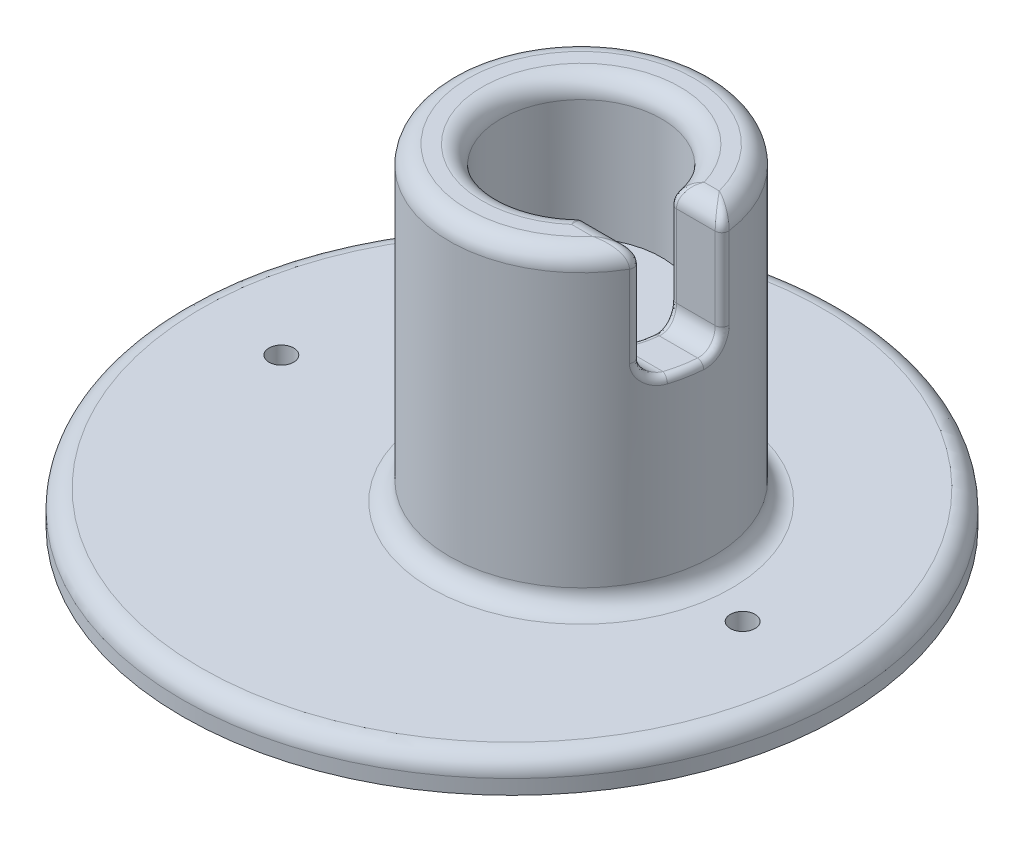
SolidWorks part; units mm, degrees
material "ABS"
ref_plane "Front Plane" through (0, 0, 0) normal (0, 0, 1) x (1, 0, 0)
ref_plane "Top Plane" through (0, 0, 0) normal (0, 1, 0) x (1, 0, 0)
ref_plane "Right Plane" through (0, 0, 0) normal (1, 0, 0) x (0, 0, -1)
sketch "Sketch1" plane through (0, 0, 0) normal (0, 1, 0) x (1, 0, 0)
  circle A0 centre (0, 0) radius 7.62
  circle A1 centre (0, 0) radius 63.5
  dimension "D1" = 127
  dimension "D2" = 15.24
extrude "Boss-Extrude1" add sketch "Sketch1" along normal blind 6.35
sketch "Sketch2" plane through (0, 6.35, 0) normal (0, 1, 0) x (1, 0, 0)
  line L0 (9, 11.3527) -> (9, -3.5148) construction
  line L1 (8.89, 4.445) -> (9, 4.445) construction
  circle A0 centre (8.89, 4.445) radius 25.4
  circle A3 centre (8.89, 4.445) radius 15.494
  dimension "D1" = 50.8
  dimension "D2" = 4.445
  dimension "D3" = 30.988
  dimension "D4" = 9
extrude "Boss-Extrude2" add sketch "Sketch2" along normal blind 59.69
sketch "Sketch3" plane through (0, 66.04, 0) normal (0, 1, 0) x (1, 0, 0)
  line L8 (43.18, 6.35) -> (43.18, -6.35)
  line L9 (-1.27, 6.35) -> (43.18, 6.35)
  line L13 (-1.27, 6.35) -> (-1.27, -6.35)
  line L14 (-1.27, -6.35) -> (43.18, -6.35)
  circle A0 centre (0, 0) radius 7.62 construction
  dimension "D5" = 6.35
  dimension "D1" = 1.27
  dimension "D2" = 12.7
  dimension "D3" = 44.45
extrude "Cut-Extrude1" cut sketch "Sketch3" against normal blind 22.86
sketch "Sketch4" plane through (0, 6.35, 0) normal (0, 1, 0) x (1, 0, 0)
  circle A0 centre (44.45, 0) radius 2.3812
  circle A1 centre (-44.45, 0) radius 2.3812
  dimension "D1" = 4.7625
  dimension "D2" = 4.7625
  dimension "D3" = 44.45
  dimension "D4" = 44.45
extrude "Cut-Extrude2" cut sketch "Sketch4" against normal through all
fillet "Fillet1" radius 3.556 8 edges at (-16.0907, 66.04, -9.041) (29.2425, 66.04, -6.35) (-5.7989, 66.04, -9.3744) (25.9432, 66.04, 6.35) (25.9432, 43.18, 6.35) (29.2425, 43.18, -6.35) (8.89, 6.35, 20.955) (0, 6.35, 63.5)
fillet "Fillet2" radius 1.27 1 edges at (22.7483, 6.35, -11.3741)
fillet "Fillet3" radius 1.27 14 edges at (20.4615, 44.9324, 5.8587) (20.2892, 64.5782, 7.032) (30.8341, 64.5341, 7.0004) (24.7056, 64.309, -6.8541) (24.3749, 43.9279, -4.9757) (33.7516, 64.1773, -6.779) (20.0045, 54.61, 6.35) (31.8819, 54.61, 6.35) (24.2664, 54.61, -6.35) (34.2185, 54.61, -6.35) (23.7082, 43.18, 0.0812) (32.4276, 44.0307, 5.1019) (33.893, 43.18, 0.028) (34.2649, 44.5173, -5.573)
sketch "Sketch5" plane through (0, 6.35, 0) normal (0, 1, 0) x (1, 0, 0)
  circle A0 centre (8.89, 4.445) radius 15.494
extrude "Boss-Extrude3" add sketch "Sketch5" along normal blind 33.02
sketch "Sketch6" plane through (0, 0, 0) normal (0, -1, 0) x (1, 0, 0)
  circle A0 centre (0, 0) radius 7.62
extrude "Cut-Extrude3" cut sketch "Sketch6" against normal blind 12.7
